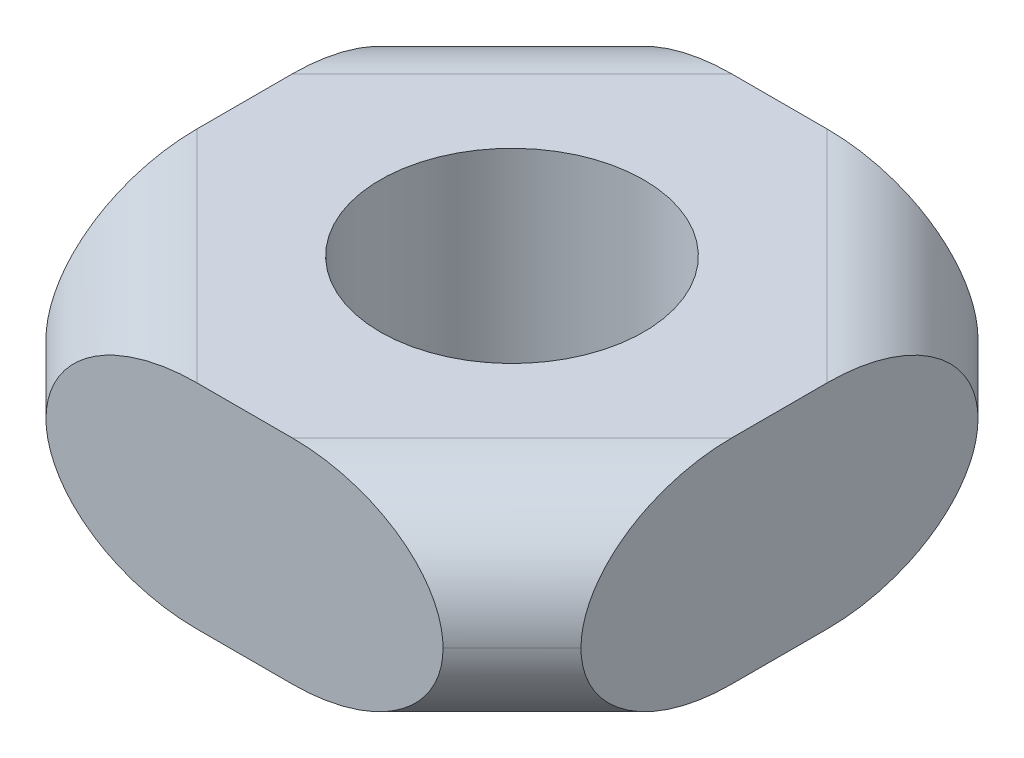
SolidWorks part; units mm, degrees
ref_plane "前视基准面" through (0, 0, 0) normal (0, 0, 1) x (1, 0, 0)
ref_plane "上视基准面" through (0, 0, 0) normal (0, 1, 0) x (1, 0, 0)
ref_plane "右视基准面" through (0, 0, 0) normal (1, 0, 0) x (0, 0, -1)
sketch "草图1" plane through (0, 0, 0) normal (0, 1, 0) x (1, 0, 0)
  line B0 (0, 0) -> (10.2416, 0)
  line B1 (12.0208, 1.7792) -> (12.0208, 12.0208)
  line B2 (10.2416, 13.8) -> (0, 13.8)
  line B3 (-1.7792, 12.0208) -> (-1.7792, 1.7792)
  line B4 (12.0208, 12.0208) -> (10.2416, 13.8)
  line B5 (0, 13.8) -> (-1.7792, 12.0208)
  line B6 (-1.7792, 1.7792) -> (0, 0)
  line B7 (10.2416, 0) -> (12.0208, 1.7792)
sketch_block_instance "A$C72BC1A54-1"
sketch_block "A$C72BC1A54"
extrude "凸台-拉伸1" add sketch "草图1" along normal blind 5.5
fillet "圆角1" radius 2.75 8 edges at (-0.8896, 0, -12.9104) (-0.8896, 5.5, -12.9104) (11.1312, 0, -12.9104) (11.1312, 5.5, -12.9104) (11.1312, 0, -0.8896) (11.1312, 5.5, -0.8896) (-0.8896, 0, -0.8896) (-0.8896, 5.5, -0.8896)
sketch "草图3" plane through (0, 5.5, 0) normal (0, 1, 0) x (1, 0, 0)
  point P0 (5.1208, 6.9)
hole_wizard "M8 螺纹孔1" positions "3D草图1" profile "草图4" tap size "M8" standard "Iso"
sketch3d "3D草图1"
  point P0 (5.1208, 5.5, -6.9)
sketch "草图4" plane through (5.1208, 5.5, -6.9) normal (1, 0, 0) x (0, 0, 1)
  line L0 (0, 0) -> (0, 21.7929)
  line L1 (0, 21.7929) -> (3.4, 19.75)
  line L2 (3.4, 19.75) -> (3.4, 0)
  line L5 (3.4, 0) -> (0, 0)
  line L10 (0, 21.7929) -> (-3.4, 19.75) construction
  line L11 (0, -6.35) -> (0, 107.95) construction
  dimension "螺纹孔钻头直径" = 6.8
  dimension "螺纹孔钻头深度" = 19.75
  dimension "导头角度" = 118
cosmetic thread "孔螺蚊线1" parameters "D1"=5.5, "D2"=8
